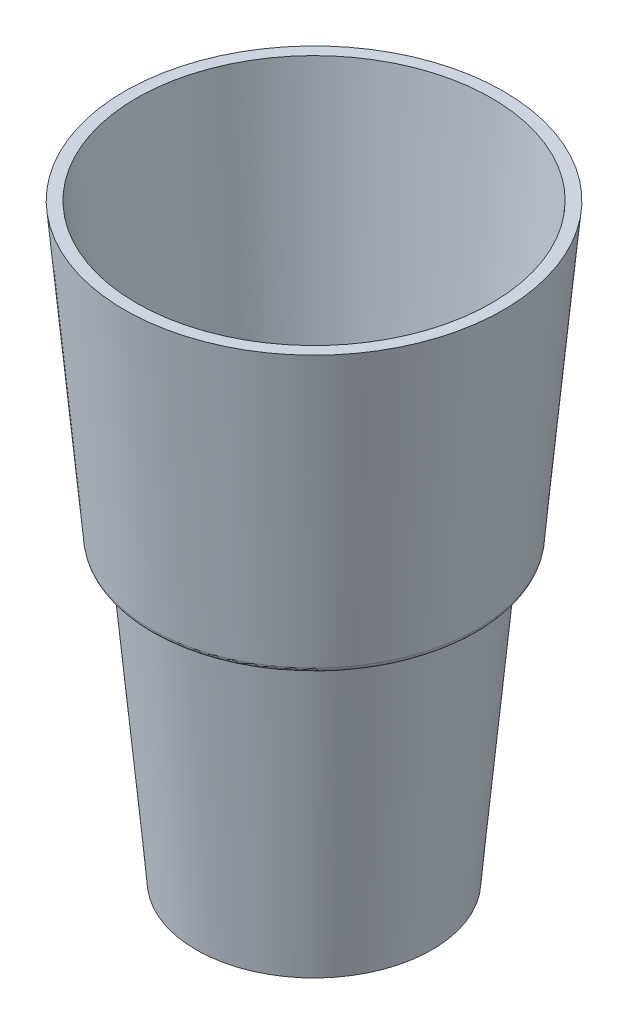
SolidWorks part; units mm, degrees
ref_plane "Front Plane" through (0, 0, 0) normal (0, 0, 1) x (1, 0, 0)
ref_plane "Top Plane" through (0, 0, 0) normal (0, 1, 0) x (1, 0, 0)
ref_plane "Right Plane" through (0, 0, 0) normal (1, 0, 0) x (0, 0, -1)
sketch "Sketch1" plane through (0, 0, 0) normal (0, 0, 1) x (1, 0, 0)
  line L0 (0, 0) -> (25.4, 0)
  line L1 (25.4, 0) -> (31.1859, 63.5)
  line L2 (31.1859, 63.5) -> (34.9959, 63.5)
  line L3 (34.9959, 63.5) -> (40.7818, 127)
  line L4 (40.7818, 127) -> (0, 127)
  line L6 (0, 0) -> (0, 127)
  dimension "D1" = 25.4
  dimension "D2" = 63.5
  dimension "D3" = 63.5
  dimension "D4" = 3.81
revolve "Revolve2" add sketch "Sketch1" angle 360 about L6
fillet "Fillet1" radius 1.27 2 edges at (0, 63.5, -34.9959) (0, 63.5, -31.1859)
shell "Shell1" thickness 2.54 removed face at (0, 127, -40.7818)
